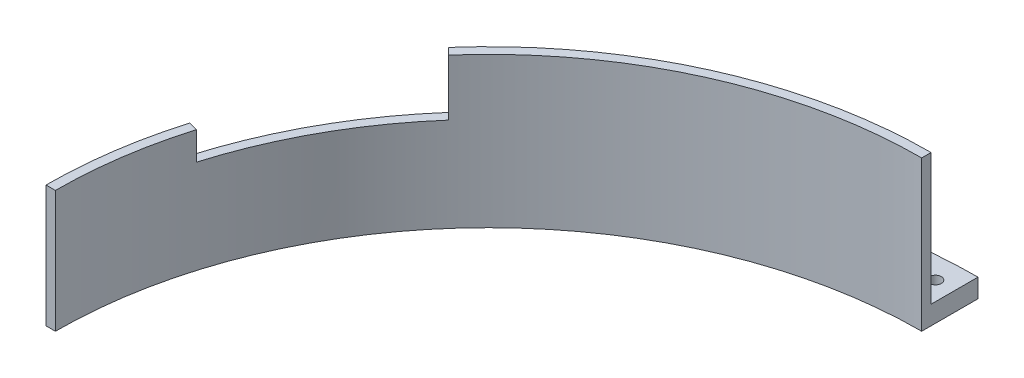
SolidWorks part; units mm, degrees
ref_plane "Front" through (0, 0, 0) normal (0, 0, 1) x (1, 0, 0)
ref_plane "Top" through (0, 0, 0) normal (0, 1, 0) x (1, 0, 0)
ref_plane "Right" through (0, 0, 0) normal (1, 0, 0) x (0, 0, -1)
sketch "Sketch1" plane through (0, 0, 0) normal (0, 1, 0) x (1, 0, 0)
  line L0 (0, 146.558) -> (0, 165.608)
  line L1 (-146.558, 0) -> (-165.608, 0)
  arc A0 (0, 146.558) -> (-146.558, 0) centre (0, 0) ccw
  arc A1 (0, 165.608) -> (-165.608, 0) centre (0, 0) ccw
  point P15 (0, 156.083)
  dimension "D2" = 146.558
  dimension "D1" = 19.05
extrude "Boss-Extrude1" add sketch "Sketch1" along normal blind 6.35 contours A0 L1 A1 L0
sketch "Sketch4" plane through (0, 6.35, 0) normal (0, 1, 0) x (1, 0, 0)
  line L2 (-149.733, 0) -> (-146.558, 0)
  line L3 (0, 146.558) -> (0, 149.733)
  line L4 (0, 146.558) -> (0, 165.608) construction
  arc A0 (-146.558, 0) -> (0, 146.558) centre (0, 0) cw
  arc A1 (0, 146.558) -> (-146.558, 0) centre (0, 0) ccw construction
  arc A2 (-149.733, 0) -> (0, 149.733) centre (0, 0) cw
  dimension "D1" = 3.175
extrude "Boss-Extrude2" add sketch "Sketch4" along normal blind 44.45
sketch "Sketch5" plane through (0, 50.8, 0) normal (0, 1, 0) x (1, 0, 0)
  line L0 (-105.8772, 105.8772) -> (-103.6322, 103.6322) construction
  line L1 (-146.558, 0) -> (-149.733, 0)
  line L2 (-112.398, 98.9276) -> (-110.1483, 96.6779)
  arc A0 (0, 149.733) -> (-149.733, 0) centre (0, 0) ccw construction
  arc A1 (0, 146.558) -> (-146.558, 0) centre (0, 0) ccw construction
  arc A2 (-110.1483, 96.6779) -> (-146.558, 0) centre (0, 0) ccw
  arc A3 (-112.398, 98.9276) -> (-149.733, 0) centre (0, 0) ccw
  dimension "D1" = 9.525
  dimension "D2" = 9.525
extrude "Cut-Extrude2" cut sketch "Sketch5" against normal blind 9.525 and the other way through all
sketch "Sketch7" plane through (0, 41.275, 0) normal (0, 1, 0) x (1, 0, 0)
  line L0 (-110.1483, 96.6779) -> (-112.398, 98.9276)
  line L1 (-137.1538, 51.6534) -> (-140.0886, 52.8691) construction
  line L2 (-143.5655, 42.5313) -> (-140.5213, 41.6294)
  line L4 (-112.398, 98.9276) -> (-110.1483, 96.6779) construction
  arc A0 (-140.5213, 41.6294) -> (-110.1483, 96.6779) centre (0, 0) cw
  arc A1 (-143.5655, 42.5313) -> (-112.398, 98.9276) centre (0, 0) cw
  arc A2 (-110.1483, 96.6779) -> (-146.558, 0) centre (0, 0) ccw construction
  arc A3 (-112.398, 98.9276) -> (-149.733, 0) centre (0, 0) ccw construction
  dimension "D1" = 6
extrude "Cut-Extrude3" cut sketch "Sketch7" against normal blind 9.525 and the other way through all from surface starting at face at (-134.1653, 41.275, -50.5813)
sketch "Sketch8" plane through (0, 6.35, 0) normal (0, 1, 0) x (1, 0, 0)
  line L1 (-149.733, 0) -> (-165.608, 0)
  line L2 (-149.733, 0) -> (-149.733, 76.2)
  line L3 (-149.733, 76.2) -> (-165.608, 76.2)
  line L4 (-165.608, 0) -> (-165.608, 76.2)
  dimension "D1" = 76.2
extrude "Cut-Extrude4" cut sketch "Sketch8" against normal through all
sketch "Sketch13" plane through (0, 6.35, 0) normal (0, 1, 0) x (1, 0, 0)
  line L0 (0, 149.733) -> (0, 165.608) construction
  line L1 (-143.383, 65.5843) -> (-87.8583, 130.9233) construction
  line L2 (-87.8583, 130.9233) -> (-6.35, 157.5426) construction
  line L4 (-149.733, 0) -> (-149.733, 70.7534) construction
  circle A0 centre (0, 0) radius 157.6705 construction
  point P0 (-6.35, 157.5426)
  point P2 (-87.8583, 130.9233)
  point P4 (-143.383, 65.5843)
  point P24 (0, 157.6705)
  dimension "D1" = 6.35
  dimension "D2" = 6.35
hole_wizard "#10-32 Tapped Hole1" positions "Sketch13" profile "Sketch12" tap size "#10-32" standard "ANSI Inch" end condition up to next
sketch "Sketch12" plane through (-6.35, 6.35, -157.5426) normal (1, 0, 0) x (0, 0, 1)
  line L0 (0, 0) -> (0, 6.35)
  line L1 (0, 6.35) -> (2.0193, 6.35)
  line L2 (2.0193, 6.35) -> (2.0193, 0)
  line L5 (2.0193, 0) -> (0, 0)
  line L11 (0, -6.35) -> (0, 107.95) construction
  dimension "Thru Tap Drill Dia." = 4.0386
  dimension "Thru Tap Drill Depth" = 6.35
cosmetic thread "Hole Thread1" parameters "D2"=4.826
cosmetic thread "Hole Thread2" parameters "D2"=4.826
cosmetic thread "Hole Thread3" parameters "D2"=4.826
